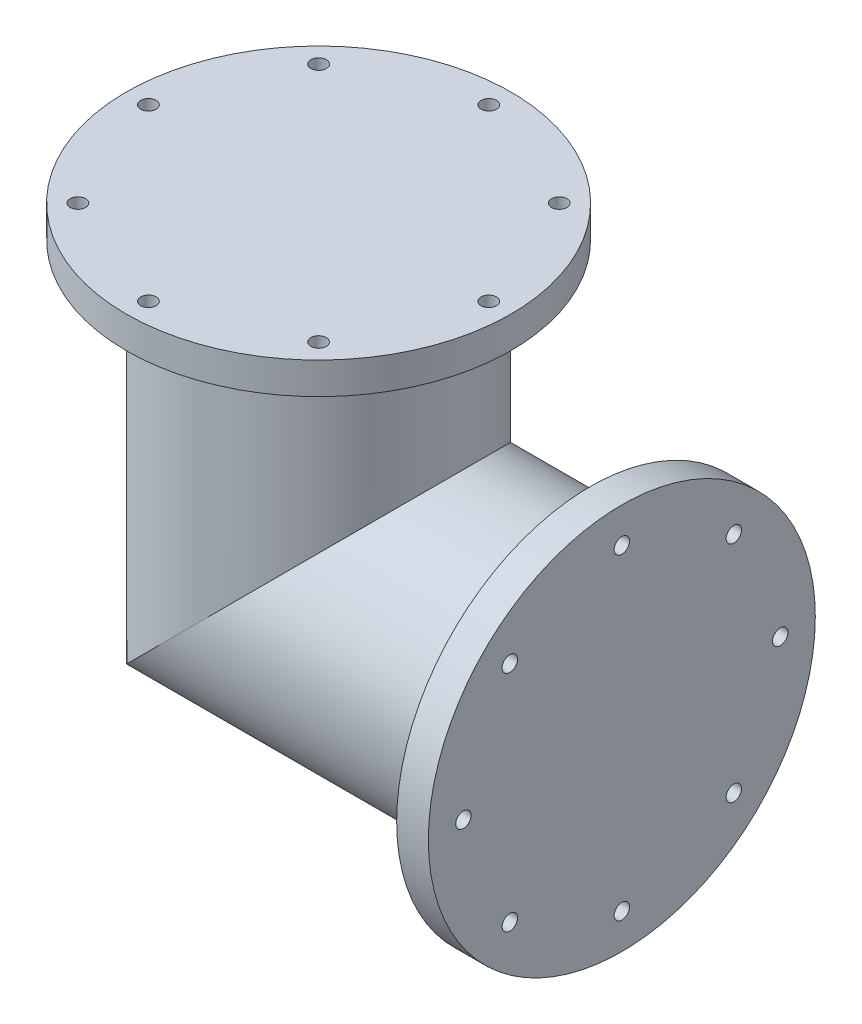
SolidWorks part; units mm, degrees
other "Elemento de detalle1"
other "Carpeta de soldadura"
other "Cordón de soldadura1"
material "6063-T5"
ref_plane "Front" through (0, 0, 0) normal (0, 0, 1) x (1, 0, 0)
ref_plane "Top" through (0, 0, 0) normal (0, 1, 0) x (1, 0, 0)
ref_plane "Right" through (0, 0, 0) normal (1, 0, 0) x (0, 0, -1)
sketch "Croquis1" plane through (0, 0, 0) normal (1, 0, 0) x (0, 0, -1)
  circle A0 centre (0, 0) radius 42.75
  dimension "D1" = 85.5
extrude "Saliente-Extruir1" add sketch "Croquis1" along normal mid plane 7
sketch "Croquis2" plane through (0, 0, 0) normal (0, 0, 1) x (1, 0, 0)
  line L0 (-13.5, -50) -> (-63.5, 0) construction
  line L2 (3.85, 0) -> (-3.85, 0) construction
  line L4 (-3.5, 42.75) -> (-3.5, -42.75) construction
  dimension "D1" = 45
  dimension "D2" = 10
  dimension "D3" = 50
ref_plane "Plano1" through (-63.5, 0, 0) normal (-0.7071, 0.7071, 0) x (0, 0, 1)
sketch "Croquis3" plane through (-3.5, 0, 0) normal (-1, 0, 0) x (0, 0, 1)
  circle A0 centre (0, 0) radius 30
  circle A1 centre (0, 0) radius 25
  dimension "D1" = 60
  dimension "D2" = 50
extrude "Saliente-Extruir2" add sketch "Croquis3" along normal up to surface (60 mm away) up to plane "Plano1"
ref_plane "Plano2" through (0, 60, 0) normal (0, 1, 0) x (1, 0, 0)
sketch "Croquis4" plane through (0, 60, 0) normal (0, 1, 0) x (1, 0, 0)
  circle A0 centre (-63.5, 0) radius 30 construction
  circle A1 centre (-63.5, 0) radius 30
  circle A2 centre (-63.5, 0) radius 25 construction
  circle A3 centre (-63.5, 0) radius 25
extrude "Saliente-Extruir3" add sketch "Croquis4" against normal up to surface (60 mm away) separate body up to face at (-38.5, 25, 0)
hole_wizard "Refrentado para tornillo con cabeza troncocónica de M31" positions "Croquis5" profile "Croquis7" counterbore size "M3" standard "Ansi Metric" end condition up to next
sketch "Croquis5" plane through (-3.5, 0, 0) normal (-1, 0, 0) x (0, 0, 1)
  line L0 (0, -47.025) -> (0, 47.025) construction
  line L1 (47.025, 0) -> (-47.025, 0) construction
  point P0 (0, 35)
  point P12 (24.7487, 24.7487)
  point P13 (35, 0)
  point P14 (24.7487, -24.7487)
  point P15 (0, -35)
  point P16 (-24.7487, -24.7487)
  point P17 (-35, 0)
  point P18 (-24.7487, 24.7487)
  dimension "D1" = 35
  dimension "D2" = 8
sketch "Croquis7" plane through (-3.5, 35, 0) normal (0, 1, 0) x (0, 0, 1)
  line L0 (0, 0) -> (0, 7)
  line L1 (0, 7) -> (1.7, 7)
  line L3 (1.7, 7) -> (1.7, 2.4)
  line L4 (1.7, 2.4) -> (3.5, 2.4)
  line L5 (3.5, 2.4) -> (3.5, 0)
  line L7 (3.5, 0) -> (0, 0)
  line L11 (0, -6.35) -> (0, 107.95) construction
  dimension "Diámetro de taladro hasta el siguiente" = 3.4
  dimension "Profundidad de taladro hasta el siguiente" = 7
  dimension "Diámetro de refrentado" = 7
  dimension "Profundidad de refrentado" = 2.4
sketch "Croquis8" plane through (0, 60, 0) normal (0, 1, 0) x (1, 0, 0)
  line L0 (-60.3625, 0) -> (60.3625, 0) construction
  circle A0 centre (-63.5, 0) radius 42.5
  circle A1 centre (-63.5, 0) radius 25 construction
  dimension "D1" = 85
extrude "Saliente-Extruir4" add sketch "Croquis8" along normal blind 7
hole_wizard "Refrentado para tornillo con cabeza troncocónica de M32" positions "Croquis9" profile "Croquis10" counterbore size "M3" standard "Ansi Metric" end condition up to next
sketch "Croquis9" plane through (0, 60, 0) normal (0, -1, 0) x (-1, 0, 0)
  line L0 (63.5, 0) -> (63.5, -37.6) construction
  line L1 (-60.225, 0) -> (60.225, 0) construction
  line L4 (63.5, 0) -> (63.5, 37.6) construction
  circle A0 centre (63.5, 0) radius 30 construction
  point P0 (63.5, -37.6)
  point P24 (36.9128, -26.5872)
  point P25 (25.9, 0)
  point P26 (36.9128, 26.5872)
  point P27 (63.5, 37.6)
  point P28 (90.0872, 26.5872)
  point P29 (101.1, 0)
  point P30 (90.0872, -26.5872)
  dimension "D1" = 37.6
  dimension "D3" = 8
sketch "Croquis10" plane through (-63.5, 60, 37.6) normal (1, 0, 0) x (0, 0, -1)
  line L0 (0, 0) -> (0, 7.001)
  line L1 (0, 7.001) -> (1.7, 7.001)
  line L3 (1.7, 7.001) -> (1.7, 2.4)
  line L4 (1.7, 2.4) -> (3.5, 2.4)
  line L5 (3.5, 2.4) -> (3.5, 0)
  line L7 (3.5, 0) -> (0, 0)
  line L11 (0, -6.35) -> (0, 107.95) construction
  dimension "Diámetro de taladro hasta el siguiente" = 3.4
  dimension "Profundidad de taladro hasta el siguiente" = 7.001
  dimension "Diámetro de refrentado" = 7
  dimension "Profundidad de refrentado" = 2.4
sketch "Croquis11" plane through (0, 0, 0) normal (0, 0, 1) x (1, 0, 0)
  line L0 (-63.5, 67) -> (-63.5, 0) construction
  line L1 (47.025, 0) -> (-47.025, 0) construction
  line L2 (-63.5, 0) -> (3.5, 0) construction
  line L3 (-21, 67) -> (-106, 67) construction
  line L4 (3.5, -42.75) -> (3.5, 42.75) construction
